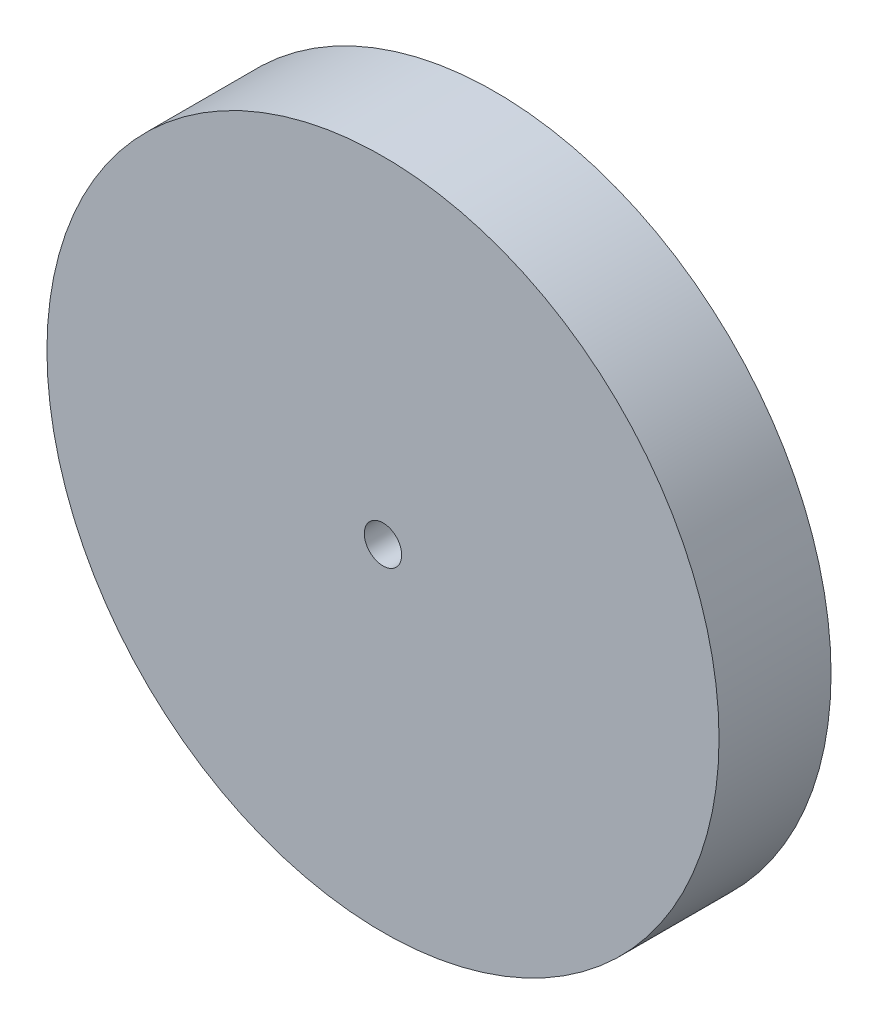
SolidWorks part; units mm, degrees
ref_plane "Front Plane" through (0, 0, 0) normal (0, 0, 1) x (1, 0, 0)
ref_plane "Top Plane" through (0, 0, 0) normal (0, 1, 0) x (1, 0, 0)
ref_plane "Right Plane" through (0, 0, 0) normal (1, 0, 0) x (0, 0, -1)
sketch "Sketch1" plane through (0, 0, 0) normal (0, 0, 1) x (1, 0, 0)
  circle A0 centre (0, 0) radius 18
  circle A1 centre (0, 0) radius 1
  dimension "D1" = 2
  dimension "D2" = 36
extrude "Boss-Extrude1" add sketch "Sketch1" along normal blind 6
